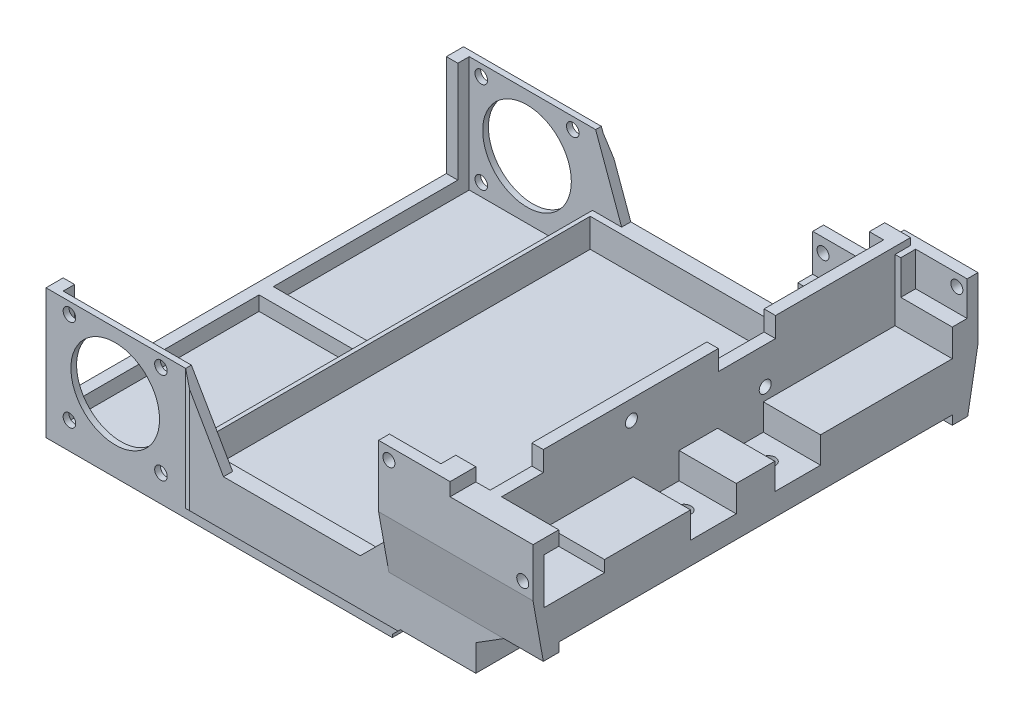
SolidWorks part; units mm, degrees
ref_plane "Front Plane" through (0, 0, 0) normal (0, 0, 1) x (1, 0, 0)
ref_plane "Top Plane" through (0, 0, 0) normal (0, 1, 0) x (1, 0, 0)
ref_plane "Right Plane" through (0, 0, 0) normal (1, 0, 0) x (0, 0, -1)
sketch "Sketch1" plane through (0, 0, 0) normal (0, 1, 0) x (1, 0, 0)
  line L0 (-12.1, 32.5) -> (-12.1, 35.5)
  line L1 (78.4, -41.4) -> (51.4, -41.4)
  line L2 (78.4, -41.4) -> (78.4, -56)
  line L3 (78.4, -56) -> (51.4, -56)
  line L4 (51.4, -41.4) -> (51.4, -56)
  line L5 (63.8, 13.5) -> (78.4, 13.5)
  line L6 (63.8, 13.5) -> (63.8, -13.5)
  line L7 (63.8, -13.5) -> (78.4, -13.5)
  line L8 (78.4, 13.5) -> (78.4, -13.5)
  line L9 (51.4, 41.4) -> (78.4, 41.4)
  line L10 (51.4, 41.4) -> (51.4, 56)
  line L11 (51.4, 56) -> (78.4, 56)
  line L12 (78.4, 41.4) -> (78.4, 56)
  line L13 (14.3, -34.25) -> (60.8, -34.25)
  line L14 (14.3, -34.25) -> (14.3, 34.25)
  line L15 (14.3, 34.25) -> (60.8, 34.25)
  line L16 (60.8, -34.25) -> (60.8, 34.25)
  line L17 (-12.1, 2.5) -> (10.1, 2.5)
  line L18 (-12.1, 2.5) -> (-12.1, 10.5)
  line L19 (-12.1, 35.5) -> (10.1, 35.5)
  line L20 (10.1, 2.5) -> (10.1, 10.5)
  line L21 (10.1, -35.5) -> (-10.1, -35.5)
  line L22 (10.1, -35.5) -> (10.1, -32.5)
  line L23 (10.1, -2.5) -> (-10.1, -2.5)
  line L24 (-10.1, -35.5) -> (-10.1, -32.5)
  line L25 (-16.1, -32.5) -> (-10.1, -32.5)
  line L26 (-16.1, -32.5) -> (-16.1, -10.5)
  line L27 (-16.1, -10.5) -> (-10.1, -10.5)
  line L28 (11.3, -32.5) -> (11.3, -10.5)
  line L29 (-16.1, 10.5) -> (-12.1, 10.5)
  line L30 (-16.1, 10.5) -> (-16.1, 32.5)
  line L31 (-16.1, 32.5) -> (-12.1, 32.5)
  line L32 (11.3, 10.5) -> (11.3, 32.5)
  line L33 (10.1, 10.5) -> (11.3, 10.5)
  line L34 (10.1, 32.5) -> (10.1, 35.5)
  line L35 (10.1, 32.5) -> (11.3, 32.5)
  line L36 (10.1, -10.5) -> (11.3, -10.5)
  line L37 (10.1, -10.5) -> (10.1, -2.5)
  line L38 (-10.1, -10.5) -> (-10.1, -2.5)
  line L39 (10.1, -32.5) -> (11.3, -32.5)
  arc A0 (66.5992, 6.7139) -> (66.5992, -6.7139) centre (70.3, 0) ccw
  arc A1 (67.5805, -8.0067) -> (73.0195, -8.0067) centre (70.3, -7.366) ccw
  arc A2 (73.0195, 8.0067) -> (67.5805, 8.0067) centre (70.3, 7.366) ccw
  arc A3 (74.0008, -6.7139) -> (74.0008, 6.7139) centre (70.3, 0) ccw
  arc A4 (73.0195, -8.0067) -> (74.0008, -6.7139) centre (74.9662, -8.4654) cw
  arc A5 (66.5992, 6.7139) -> (67.5805, 8.0067) centre (65.6338, 8.4654) ccw
  arc A6 (67.5805, -8.0067) -> (66.5992, -6.7139) centre (65.6338, -8.4654) ccw
  arc A7 (74.0008, 6.7139) -> (73.0195, 8.0067) centre (74.9662, 8.4654) cw
  point P33 (73.085, -7.1425)
  point P50 (78.4, 0)
  point P56 (14.3, 0)
  dimension "D1" = 2
  dimension "D2" = 2
  dimension "D3" = 2
  dimension "D36" = 7.6663
  dimension "D37" = 7.366
  dimension "D39" = 2.794
  dimension "D4" = 22.2
  dimension "D5" = 3
  dimension "D6" = 22
  dimension "D7" = 4
  dimension "D8" = 1.2
  dimension "D9" = 3
  dimension "D10" = 46.5
  dimension "D11" = 68.5
  dimension "D12" = 20.2
  dimension "D13" = 6
  dimension "D14" = 1.2
  dimension "D15" = 3
  dimension "D16" = 22
  dimension "D17" = 8
  dimension "D18" = 3
  dimension "D19" = 20.5
  dimension "D20" = 20.5
  dimension "D21" = 27
  dimension "D22" = 14.6
  dimension "D23" = 27
  dimension "D24" = 14.6
  dimension "D27" = 8
  dimension "D28" = 5
  dimension "D29" = 7.15
  dimension "D30" = 3
  dimension "D32" = 9.5
  dimension "D34" = 27
  dimension "D35" = 14.6
  dimension "D38" = 7.366
  dimension "D40" = 14.3
  dimension "D41" = 2.5
sketch "Sketch5" plane through (0, 0, 0) normal (0, 1, 0) x (1, 0, 0)
  line L0 (63.65, 37.1) -> (11.45, 37.1)
  line L1 (60.8, 34.25) -> (14.3, 34.25) construction
  line L2 (60.8, 34.25) -> (60.8, -34.25) construction
  line L3 (60.8, -34.25) -> (14.3, -34.25) construction
  line L4 (14.3, 34.25) -> (14.3, -34.25) construction
  line L5 (11.45, 37.1) -> (11.45, -37.1)
  line L6 (63.65, -37.1) -> (11.45, -37.1)
  line L7 (63.65, 37.1) -> (63.65, 3.8718)
  line L8 (63.65, -3.8718) -> (63.65, -37.1)
  line L9 (14.15, 34.4) -> (14.15, -34.4)
  line L10 (63.65, 37.1) -> (63.65, -37.1) construction
  line L11 (60.95, -34.4) -> (14.15, -34.4)
  line L12 (60.95, 34.4) -> (60.95, -34.4)
  line L13 (60.95, 34.4) -> (14.15, 34.4)
  arc A0 (63.65, 3.8718) -> (63.65, -3.8718) centre (70.3, 0) ccw
  dimension "D2" = 15.39
  dimension "D1" = 2.85
  dimension "D3" = 0.15
extrude "Boss-Extrude2" add sketch "Sketch5" along normal blind 5
sketch "Sketch6" plane through (0, 0, 0) normal (0, -1, 0) x (1, 0, 0)
  line L0 (63.65, -3.8718) -> (63.65, -37.1)
  line L1 (11.45, 37.1) -> (63.65, 37.1)
  line L2 (11.45, 37.1) -> (11.45, -37.1)
  line L3 (11.45, -37.1) -> (63.65, -37.1)
  line L4 (63.65, 37.1) -> (63.65, 3.8718)
  arc A0 (63.65, 3.8718) -> (63.65, -3.8718) centre (70.3, 0) ccw
  dimension "D1" = 15.39
extrude "Boss-Extrude4" add sketch "Sketch6" along normal blind 2.7
sketch "Sketch7" plane through (0, 5, 0) normal (0, 1, 0) x (1, 0, 0)
  line L1 (63.65, -37.1) -> (55.65, -37.1)
  line L2 (11.45, -37.1) -> (63.65, -37.1) construction
  line L3 (55.65, -37.1) -> (55.65, -34.4)
  line L4 (14.15, -34.4) -> (60.95, -34.4) construction
  line L5 (55.65, -34.4) -> (60.95, -34.4)
  line L6 (60.95, -34.4) -> (60.95, 34.4)
  line L7 (60.95, 34.4) -> (55.65, 34.4)
  line L8 (60.95, 34.4) -> (14.15, 34.4) construction
  line L9 (55.65, 34.4) -> (55.65, 37.1)
  line L10 (63.65, 37.1) -> (11.45, 37.1) construction
  line L11 (55.65, 37.1) -> (63.65, 37.1)
  line L14 (63.65, 37.1) -> (63.65, 3.8718)
  line L15 (63.65, -3.8718) -> (63.65, -37.1)
  arc A0 (63.65, 3.8718) -> (63.65, -3.8718) centre (70.3, 0) ccw
  dimension "D1" = 15.39
  dimension "D2" = 8
  dimension "D3" = 8
extrude "Boss-Extrude5" add sketch "Sketch7" along normal blind 1.575
sketch "Sketch8" plane through (0, 6.575, 0) normal (0, 1, 0) x (1, 0, 0)
  line L0 (55.65, -37.1) -> (63.65, -37.1) construction
  line L1 (60.95, -37.1) -> (78.45, -37.1)
  line L2 (60.95, -37.1) -> (60.95, 37.1)
  line L3 (60.95, 37.1) -> (78.45, 37.1)
  line L4 (78.45, -37.1) -> (78.45, 37.1)
  line L5 (60.95, -37.1) -> (63.65, -37.1) construction
  line L6 (63.65, 37.1) -> (55.65, 37.1) construction
  point P6 (0, 0)
  point P11 (0, 0)
  dimension "D2" = 17.5
  dimension "D3" = 2.7
extrude "Boss-Extrude6" add sketch "Sketch8" along normal blind 8.5
sketch "Sketch9" plane through (0, 0, 37.1) normal (0, 0, 1) x (1, 0, 0)
  line L0 (60.95, 15.075) -> (55.65, 6.575)
  line L1 (55.65, 6.575) -> (60.95, 6.575)
  line L2 (60.95, 6.575) -> (60.95, 15.075)
extrude "Boss-Extrude7" add sketch "Sketch9" against normal through all
sketch "Sketch10" plane through (0, 0, 0) normal (0, 1, 0) x (1, 0, 0)
  line L0 (60.95, 37.1) -> (60.95, -37.1) construction
  line L1 (14.15, 34.4) -> (60.95, 34.4)
  line L2 (14.15, 34.4) -> (14.15, -34.4)
  line L3 (14.15, -34.4) -> (60.95, -34.4)
  line L4 (60.95, 34.4) -> (60.95, -34.4)
  line L5 (14.15, -34.4) -> (60.95, -34.4) construction
extrude "Cut-Extrude1" cut sketch "Sketch10" along normal through all
sketch "Sketch11" plane through (0, 0, 37.1) normal (0, 0, 1) x (1, 0, 0)
  line L0 (71.05, 6.575) -> (63.65, 1.9375)
  line L1 (63.65, 6.575) -> (78.45, 6.575) construction
  line L2 (63.65, 6.575) -> (63.65, -2.7) construction
  line L3 (63.65, 1.9375) -> (63.65, 6.575)
  line L4 (63.65, 6.575) -> (71.05, 6.575)
extrude "Boss-Extrude8" add sketch "Sketch11" against normal blind 5
sketch "Sketch12" plane through (0, 0, -37.1) normal (0, 0, -1) x (-1, 0, 0)
  line L0 (-71.05, 6.575) -> (-63.65, 1.9375)
  line L1 (-78.45, 6.575) -> (-63.65, 6.575) construction
  line L2 (-63.65, 6.575) -> (-63.65, -2.7) construction
  line L3 (-63.65, 1.9375) -> (-63.65, 6.575)
  line L4 (-63.65, 6.575) -> (-71.05, 6.575)
extrude "Boss-Extrude9" add sketch "Sketch12" against normal blind 5
sketch "Sketch13" plane through (0, 15.075, 0) normal (0, 1, 0) x (1, 0, 0)
  line L0 (60.95, -37.1) -> (78.45, -37.1) construction
  line L1 (60.95, 37.1) -> (65.45, 37.1)
  line L2 (60.95, 37.1) -> (60.95, -37.1)
  line L3 (60.95, -37.1) -> (65.45, -37.1)
  line L4 (65.45, 37.1) -> (65.45, -37.1)
  point P5 (0, 0)
  dimension "D1" = 4.5
extrude "Boss-Extrude10" add sketch "Sketch13" along normal blind 12
sketch "Sketch15" plane through (0, 15.075, 0) normal (0, 1, 0) x (1, 0, 0)
  circle A0 centre (70.3, 7.366) radius 1.25
  circle A1 centre (70.3, -7.366) radius 1.25
  dimension "D1" = 2.5
  dimension "D2" = 2.5
extrude "Cut-Extrude3" cut sketch "Sketch15" against normal through all
sketch "Sketch16" plane through (0, 15.075, 0) normal (0, 1, 0) x (1, 0, 0)
  line L0 (70.3, -7.366) -> (70.3, 7.366) construction
  line L1 (70.3, -7.366) -> (65.45, -7.366) construction
  line L2 (65.45, -37.1) -> (65.45, 37.1) construction
  line L3 (65.45, -7.366) -> (65.45, -11.366) construction
  line L4 (70.3, 7.366) -> (65.45, 7.366) construction
  line L5 (65.45, -37.1) -> (65.45, 37.1) construction
  line L6 (65.45, 7.366) -> (65.45, 11.366) construction
  line L7 (78.45, -37.1) -> (78.45, 37.1) construction
  line L8 (65.45, 11.366) -> (78.45, 11.366)
  line L9 (65.45, 11.366) -> (65.45, 3.366)
  line L10 (65.45, -11.366) -> (78.45, -11.366)
  line L11 (78.45, 11.366) -> (78.45, 3.366)
  line L12 (65.45, -7.366) -> (65.45, -3.366) construction
  line L13 (65.45, -3.366) -> (78.45, -3.366)
  line L14 (65.45, 7.366) -> (65.45, 3.366) construction
  line L15 (65.45, 3.366) -> (78.45, 3.366)
  line L16 (65.45, -3.366) -> (65.45, -11.366)
  line L17 (78.45, -3.366) -> (78.45, -11.366)
  dimension "D1" = 4
  dimension "D2" = 4
  dimension "D3" = 4
  dimension "D4" = 4
extrude "Cut-Extrude4" cut sketch "Sketch16" against normal offset from surface (4.6 mm away) 3.9 up to face at (70.3, 6.575, -8.616)
sketch "Sketch17" plane through (0, 15.075, 0) normal (0, 1, 0) x (1, 0, 0)
  line L0 (65.45, -37.1) -> (78.45, -37.1) construction
  line L1 (78.45, 37.1) -> (75.45, 37.1)
  line L2 (78.45, 37.1) -> (78.45, -37.1)
  line L3 (78.45, -37.1) -> (75.45, -37.1)
  line L4 (75.45, 37.1) -> (75.45, -37.1)
  dimension "D1" = 3
extrude "Cut-Extrude5" cut sketch "Sketch17" against normal through all
sketch "Sketch18" plane through (60.95, 0, 0) normal (-1, 0, 0) x (0, 0, 1)
  line L0 (0, 27.075) -> (-13.5, 27.075) construction
  line L1 (-37.1, 27.075) -> (37.1, 27.075) construction
  line L3 (-13.5, 27.075) -> (-3.5, 27.075)
  line L4 (-13.5, 27.075) -> (-13.5, 23.575)
  line L5 (-13.5, 23.575) -> (-3.5, 23.575)
  line L6 (-3.5, 27.075) -> (-3.5, 23.575)
  dimension "D1" = 13.5
  dimension "D2" = 8.5
  dimension "D3" = 10
extrude "Cut-Extrude6" cut sketch "Sketch18" against normal through all
sketch "Sketch19" plane through (65.45, 0, 0) normal (1, 0, 0) x (0, 0, -1)
  line L0 (-37.1, 27.075) -> (37.1, 27.075) construction
  line L1 (0, 15.075) -> (0, 25.875) construction
  line L3 (-11.7, 20.475) -> (11.7, 20.475) construction
  line L4 (11.7, 20.475) -> (11.7, 17.175) construction
  line L5 (-11.7, 20.475) -> (-11.7, 23.775) construction
  line L7 (0, 27.075) -> (0, 25.875) construction
  line L8 (3.366, 15.075) -> (-3.366, 15.075) construction
  circle A0 centre (-11.7, 23.775) radius 1.05
  circle A1 centre (11.7, 17.175) radius 1.05
  point P11 (0, 20.475)
  point P15 (0, 20.475)
  dimension "D3" = 2.1
  dimension "D4" = 2.1
  dimension "D1" = 23.4
  dimension "D2" = 2.1
  dimension "D5" = 10.8
extrude "Cut-Extrude7" cut sketch "Sketch19" against normal through all
sketch "Sketch20" plane through (0, 27.075, 0) normal (0, 1, 0) x (1, 0, 0)
  line L2 (60.95, -34.4) -> (60.95, 34.4)
  line L4 (63.45, -34.4) -> (63.45, 34.4)
  line L5 (60.95, 27.1) -> (60.95, 34.4) construction
  line L6 (60.95, 34.4) -> (63.45, 34.4)
  line L7 (60.95, -37.1) -> (60.95, -34.4) construction
  line L8 (60.95, -34.4) -> (63.45, -34.4)
  dimension "D1" = 2
extrude "Cut-Extrude8" cut sketch "Sketch20" against normal blind 20
sketch "Sketch21" plane through (0, 0, 37.1) normal (0, 0, 1) x (1, 0, 0)
  line L0 (75.45, 15.075) -> (75.45, 17.175) construction
  line L1 (65.45, 15.075) -> (75.45, 15.075)
  line L2 (65.45, 15.075) -> (65.45, 20.075)
  line L3 (65.45, 20.075) -> (75.45, 20.075)
  line L4 (75.45, 15.075) -> (75.45, 20.075)
  line L5 (75.45, 17.175) -> (73.65, 17.175) construction
  line L6 (75.45, 6.575) -> (75.45, 15.075) construction
  circle A0 centre (73.65, 17.175) radius 1.05
  dimension "D4" = 2.1
  dimension "D1" = 5
  dimension "D2" = 2.1
  dimension "D3" = 1.8
extrude "Boss-Extrude11" add sketch "Sketch21" against normal blind 2.7 and the other way blind 1.8
sketch "Sketch23" plane through (0, 0, 37.1) normal (0, 0, 1) x (1, 0, 0)
  line L0 (48.45, 25.875) -> (48.45, 23.775) construction
  line L1 (75.45, 15.075) -> (48.45, 15.075)
  line L2 (75.45, 15.075) -> (75.45, 25.875)
  line L3 (75.45, 25.875) -> (48.45, 25.875)
  line L4 (48.45, 15.075) -> (48.45, 25.875)
  line L5 (48.45, 23.775) -> (50.25, 23.775) construction
  circle A0 centre (50.25, 23.775) radius 1.05
  circle A1 centre (73.65, 17.175) radius 1.05
  dimension "D5" = 2.1
  dimension "D6" = 2.1
  dimension "D1" = 10.8
  dimension "D2" = 27
  dimension "D3" = 2.1
  dimension "D4" = 1.8
extrude "Boss-Extrude13" add sketch "Sketch23" along normal blind 1.8 and the other way blind 2.7
sketch "Sketch22" plane through (63.45, 0, 0) normal (-1, 0, 0) x (0, 0, 1)
  line L1 (38.9, 27.075) -> (27.1, 27.075)
  line L3 (31.375, 23.575) -> (27.1, 23.575)
  line L4 (27.1, 27.075) -> (27.1, 23.575)
  line L5 (38.9, 27.075) -> (38.9, 23.575)
  line L6 (38.9, 23.575) -> (31.375, 23.575)
  line L7 (37.1, 27.075) -> (-3.5, 27.075) construction
  line L8 (38.9, 15.075) -> (38.9, 25.875) construction
  point P5 (0, 0)
  point P6 (0, 0)
  point P10 (0, 0)
  dimension "D1" = 10
  dimension "D3" = 3.5
extrude "Cut-Extrude9" cut sketch "Sketch22" against normal through all and the other way up to surface (2.5 mm away) other way up to face at (60.95, 26.475, 35.75)
sketch "Sketch24" plane through (0, 0, 37.1) normal (0, 0, 1) x (1, 0, 0)
  line L0 (75.45, 6.575) -> (75.45, 15.075) construction
  line L1 (48.45, 15.075) -> (75.45, 15.075)
  line L2 (48.45, 15.075) -> (48.45, 5)
  line L3 (48.45, 5) -> (75.45, 5)
  line L4 (75.45, 15.075) -> (75.45, 5)
  point P5 (0, 0)
extrude "Boss-Extrude14" add sketch "Sketch24" against normal up to surface (2.7 mm away) up to face at (51.3962, 12.2904, 34.4)
sketch "Sketch25" plane through (0, 0, -37.1) normal (0, 0, -1) x (-1, 0, 0)
  line L0 (-75.45, 25.875) -> (-75.45, 23.775) construction
  line L1 (-75.45, 15.075) -> (-48.45, 15.075)
  line L2 (-75.45, 15.075) -> (-75.45, 25.875)
  line L3 (-75.45, 25.875) -> (-62.55, 25.875)
  line L5 (-75.45, 23.775) -> (-73.65, 23.775) construction
  line L6 (-48.45, 15.075) -> (-48.45, 17.175) construction
  line L7 (-48.45, 17.175) -> (-50.25, 17.175) construction
  line L9 (-48.45, 19.575) -> (-57.45, 19.575)
  line L10 (-57.45, 19.575) -> (-62.55, 25.875)
  line L11 (-48.45, 19.575) -> (-48.45, 15.075)
  circle A0 centre (-73.65, 23.775) radius 1.05
  circle A1 centre (-50.25, 17.175) radius 1.05
  dimension "D3" = 2.1
  dimension "D1" = 2.1
  dimension "D2" = 1.8
  dimension "D4" = 2.1
  dimension "D5" = 1.8
  dimension "D6" = 4.5
  dimension "D7" = 9
  dimension "D8" = 27
  dimension "D9" = 12.9
  dimension "D10" = 6.3
extrude "Boss-Extrude15" add sketch "Sketch25" along normal blind 1.8 and the other way blind 2.7
sketch "Sketch26" plane through (0, 0, -34.4) normal (0, 0, 1) x (1, 0, 0)
  line L0 (60.95, 15.075) -> (48.45, 15.075) construction
  line L1 (48.45, 19.575) -> (57.45, 19.575)
  line L2 (48.45, 19.575) -> (48.45, 15.075)
  line L3 (48.45, 15.075) -> (57.45, 15.075)
  line L4 (57.45, 19.575) -> (57.45, 15.075)
  point P7 (0, 0)
extrude "Cut-Extrude10" cut sketch "Sketch26" against normal blind 2.6
sketch "Sketch27" plane through (0, 0, 34.4) normal (0, 0, -1) x (-1, 0, 0)
  line L1 (-48.45, 25.875) -> (-57.45, 25.875)
  line L2 (-48.45, 25.875) -> (-48.45, 19.875)
  line L3 (-48.45, 19.875) -> (-57.45, 19.875)
  line L4 (-57.45, 25.875) -> (-57.45, 19.875)
  dimension "D1" = 6
  dimension "D2" = 9
extrude "Cut-Extrude11" cut sketch "Sketch27" against normal blind 2.6
sketch "Sketch28" plane through (0, 0, -34.4) normal (0, 0, 1) x (1, 0, 0)
  line L1 (75.45, 25.875) -> (66.45, 25.875)
  line L2 (75.45, 25.875) -> (75.45, 19.875)
  line L3 (75.45, 19.875) -> (66.45, 19.875)
  line L4 (66.45, 25.875) -> (66.45, 19.875)
  dimension "D1" = 6
  dimension "D2" = 9
extrude "Cut-Extrude12" cut sketch "Sketch28" against normal blind 2.6
sketch "Sketch29" plane through (0, 0, 34.4) normal (0, 0, -1) x (-1, 0, 0)
  line L0 (-75.45, 15.075) -> (-75.45, 13.075)
  line L2 (-75.45, 15.075) -> (-75.45, 21.075)
  line L3 (-75.45, 21.075) -> (-66.45, 21.075)
  line L5 (-75.45, 13.075) -> (-66.45, 13.075)
  line L6 (-66.45, 13.075) -> (-66.45, 21.075)
  dimension "D1" = 6
  dimension "D2" = 9
  dimension "D3" = 2
extrude "Cut-Extrude13" cut sketch "Sketch29" against normal blind 2.6 and the other way blind 8
sketch "Sketch30" plane through (0, 0, -37.1) normal (0, 0, -1) x (-1, 0, 0)
  line L0 (-75.45, 6.575) -> (-75.45, 15.075) construction
  line L1 (-48.45, 15.075) -> (-75.45, 15.075)
  line L2 (-48.45, 15.075) -> (-48.45, 5)
  line L3 (-48.45, 5) -> (-75.45, 5)
  line L4 (-75.45, 15.075) -> (-75.45, 5)
  line L5 (-48.45, 19.875) -> (-48.45, 5) construction
  line L6 (-55.65, 5) -> (-11.45, 5) construction
  point P5 (0, 0)
  point P8 (-50.45, 8.4749)
  point P11 (0, 0)
extrude "Boss-Extrude16" add sketch "Sketch30" against normal blind 2.7
sketch "Sketch31" plane through (0, -2.7, 0) normal (0, -1, 0) x (1, 0, 0)
  line L0 (63.65, 37.1) -> (57.15, 37.1) construction
  line L1 (63.65, 37.1) -> (11.45, 37.1) construction
  line L12 (-10.1, 35.5) -> (-10.1, 36.5) construction
  line L13 (-12.1, -35.5) -> (-12.1, -36.5) construction
  line L14 (48.45, -34.4) -> (48.45, -37) construction
  line L15 (-12.1, -36.5) -> (48.45, -36.5)
  line L16 (-12.1, -36.5) -> (-12.1, 36.5)
  line L17 (-12.1, 36.5) -> (48.45, 36.5)
  line L19 (48.45, 37) -> (48.45, 34.4) construction
  line L20 (48.45, -36.5) -> (48.45, 36.5)
  dimension "D1" = 6.5
  dimension "D2" = 1
  dimension "D3" = 1
extrude "Boss-Extrude17" add sketch "Sketch31" along normal blind 2.5
sketch "Sketch56" plane through (0, -2.7, 0) normal (0, 1, 0) x (1, 0, 0)
  line L0 (11.45, -36.5) -> (11.45, 36.5) construction
  line L1 (-12.1, -36.5) -> (11.45, -36.5)
  line L2 (-12.1, -36.5) -> (-12.1, -35.5)
  line L3 (-12.1, -35.5) -> (11.45, -35.5)
  line L4 (11.45, -36.5) -> (11.45, -35.5)
  dimension "D1" = 1
extrude "Boss-Extrude36" add sketch "Sketch56" along normal blind 20.2
sketch "Sketch58" plane through (0, -2.7, 0) normal (0, 1, 0) x (1, 0, 0)
  line L0 (11.45, 37.1) -> (11.45, -35.5) construction
  line L1 (-12.1, 35.5) -> (11.45, 35.5)
  line L2 (-12.1, 35.5) -> (-12.1, 36.5)
  line L3 (-12.1, 36.5) -> (11.45, 36.5)
  line L4 (11.45, 35.5) -> (11.45, 36.5)
  line L5 (-12.1, 36.5) -> (11.45, 36.5) construction
extrude "Boss-Extrude37" add sketch "Sketch58" along normal blind 20.2
sketch "Sketch57" plane through (0, 0, 36.5) normal (0, 0, 1) x (1, 0, 0)
  line L0 (10.1, 0) -> (-10.1, 0) construction
  line L3 (8, 17.5) -> (8, 15.5) construction
  line L4 (8, 15.5) -> (-8, 15.5) construction
  line L5 (-8, 15.5) -> (-8, -0.5) construction
  line L6 (8, 15.5) -> (8, -0.5) construction
  line L7 (0, 15.5) -> (0, 7.5) construction
  line L8 (0, 7.5) -> (-8, 7.5) construction
  line L9 (10.1, 0) -> (-10.1, 0) construction
  line L10 (10.1, 0) -> (11.3, 0) construction
  line L11 (0, 0) -> (0, 17.5) construction
  line L12 (-12.1, 17.5) -> (11.45, 17.5) construction
  line L13 (0, 17.5) -> (8, 17.5) construction
  circle A0 centre (-8, 15.5) radius 1.1
  circle A1 centre (8, 15.5) radius 1.1
  circle A2 centre (-8, -0.5) radius 1.1
  circle A3 centre (8, -0.5) radius 1.1
  circle A4 centre (0, 7.5) radius 7.75
  point P25 (0, 0)
  dimension "D6" = 2.2
  dimension "D7" = 15.5
  dimension "D1" = 8
  dimension "D2" = 2
  dimension "D3" = 16
  dimension "D4" = 16
  dimension "D5" = 16
extrude "Cut-Extrude18" cut sketch "Sketch57" against normal through all
sketch "Sketch33" plane through (0, -5.2, 0) normal (0, -1, 0) x (1, 0, 0)
  line L0 (-12.1, 0) -> (0, 0) construction
  line L4 (0, 0) -> (11.45, 0) construction
  line L6 (-12.1, -1.25) -> (0, -1.25)
  line L7 (0, -1.25) -> (11.45, -1.25)
  line L14 (-12.1, 1.25) -> (0, 1.25)
  line L16 (0, 1.25) -> (11.45, 1.25)
  line L17 (-12.1, -1.25) -> (-12.1, 1.25)
  line L18 (11.45, -1.25) -> (11.45, 1.25)
  line L19 (-12.1, 35.5) -> (-12.1, -35.5) construction
  line L20 (11.45, -37.1) -> (11.45, -36.5) construction
  point P0 (-12.6, 0)
  point P7 (0, 0)
  point P14 (0, 0)
  dimension "D1" = 1.25
  dimension "D2" = 1.25
extrude "Boss-Extrude18" add sketch "Sketch33" against normal blind 5
sketch "Sketch49" plane through (0, -2.7, 0) normal (0, 1, 0) x (1, 0, 0)
  line L0 (11.45, 36.5) -> (-12.1, 36.5) construction
  line L5 (-12.1, -36.5) -> (-10.1, -36.5)
  line L6 (-12.1, -36.5) -> (-12.1, 36.5)
  line L7 (-12.1, 36.5) -> (-10.1, 36.5)
  line L8 (-10.1, -36.5) -> (-10.1, 36.5)
  line L9 (-10.1, -10.5) -> (-10.1, -2.5) construction
extrude "Boss-Extrude33" add sketch "Sketch49" along normal blind 2.5
chamfer "Chamfer3" distance 5 angle 45 2 edges at (48.45, 5, -35.75) (48.45, 5, 35.75)
sketch "Sketch50" plane through (0, 15.075, 0) normal (0, 1, 0) x (1, 0, 0)
  line L1 (48.45, 34.4) -> (57.45, 34.4)
  line L2 (48.45, 34.4) -> (48.45, 37)
  line L3 (48.45, 37) -> (57.45, 37)
  line L4 (57.45, 34.4) -> (57.45, 37)
extrude "Cut-Extrude16" cut sketch "Sketch50" against normal blind 2
sketch "Sketch51" plane through (75.45, 0, 0) normal (1, 0, 0) x (0, 0, -1)
  line L3 (-38.9, 15.075) -> (-37.1, 15.075)
  line L4 (-37.1, 15.075) -> (-37.1, 5)
  line L5 (-37.1, 5) -> (-38.9, 15.075)
extrude "Boss-Extrude34" add sketch "Sketch51" against normal up to surface (27 mm away) up to face at (48.45, 17.7063, 36.85)
sketch "Sketch52" plane through (75.45, 0, 0) normal (1, 0, 0) x (0, 0, -1)
  line L3 (38.9, 15.075) -> (37.1, 15.075)
  line L4 (37.1, 15.075) -> (37.1, 5)
  line L5 (37.1, 5) -> (38.9, 15.075)
extrude "Boss-Extrude35" add sketch "Sketch52" against normal up to surface (27 mm away) up to face at (48.45, 14.4312, -36.85)
sketch "Sketch53" plane through (0, 5, 0) normal (0, 1, 0) x (1, 0, 0)
  line L0 (14.15, -34.4) -> (60.95, -34.4) construction
  line L1 (14.15, 34.4) -> (12.15, 34.4)
  line L2 (14.15, 34.4) -> (14.15, -34.4)
  line L3 (14.15, -34.4) -> (12.15, -34.4)
  line L4 (12.15, 34.4) -> (12.15, -34.4)
  dimension "D1" = 2
extrude "Cut-Extrude17" cut sketch "Sketch53" against normal up to surface (5 mm away) up to face at (37.55, 0, 0)
chamfer "Chamfer4" distance 1 angle 45 1 edges at (29.95, -2.7, 36.5)
chamfer "Chamfer5" distance 2 angle 45 1 edges at (48.45, -2.7, 0.3)
chamfer "Chamfer6" distance 1 angle 45 1 edges at (30.95, -2.7, -36.5)
chamfer "Chamfer7" distance 1 angle 65 1 edges at (11.45, 0.95, 37.1) first distance on face at (11.45, 0.8, 36.8)
chamfer "Chamfer8" distance 1 angle 65 1 edges at (11.45, 0.95, -37.1) first distance on face at (11.45, 0.8, -36.8)
chamfer "Chamfer9" distance 14 angle 20 1 edges at (11.45, 5, -36) first distance on face at (11.45, 11.25, -36)
chamfer "Chamfer10" distance 14 angle 30 1 edges at (11.45, 5, 36) first distance on face at (11.45, 11.25, 36)
sketch "Sketch59" plane through (0, -0.2, 0) normal (0, 1, 0) x (1, 0, 0)
  line L0 (-10.1, -35.5) -> (-10.1, -1.25) construction
  line L1 (-12.1, -36.5) -> (-10.1, -36.5)
  line L2 (-12.1, -36.5) -> (-12.1, -33.5)
  line L3 (-12.1, -33.5) -> (-10.1, -33.5)
  line L4 (-10.1, -36.5) -> (-10.1, -33.5)
  line L5 (-10.1, 1.25) -> (-10.1, 35.5) construction
  line L6 (-12.1, 36.5) -> (-10.1, 36.5)
  line L7 (-12.1, 36.5) -> (-12.1, 33.5)
  line L8 (-12.1, 33.5) -> (-10.1, 33.5)
  line L9 (-10.1, 36.5) -> (-10.1, 33.5)
  dimension "D1" = 3
  dimension "D2" = 3
extrude "Boss-Extrude38" add sketch "Sketch59" along normal up to surface (17.7 mm away) up to face at (-0.052, 17.5, -36)
